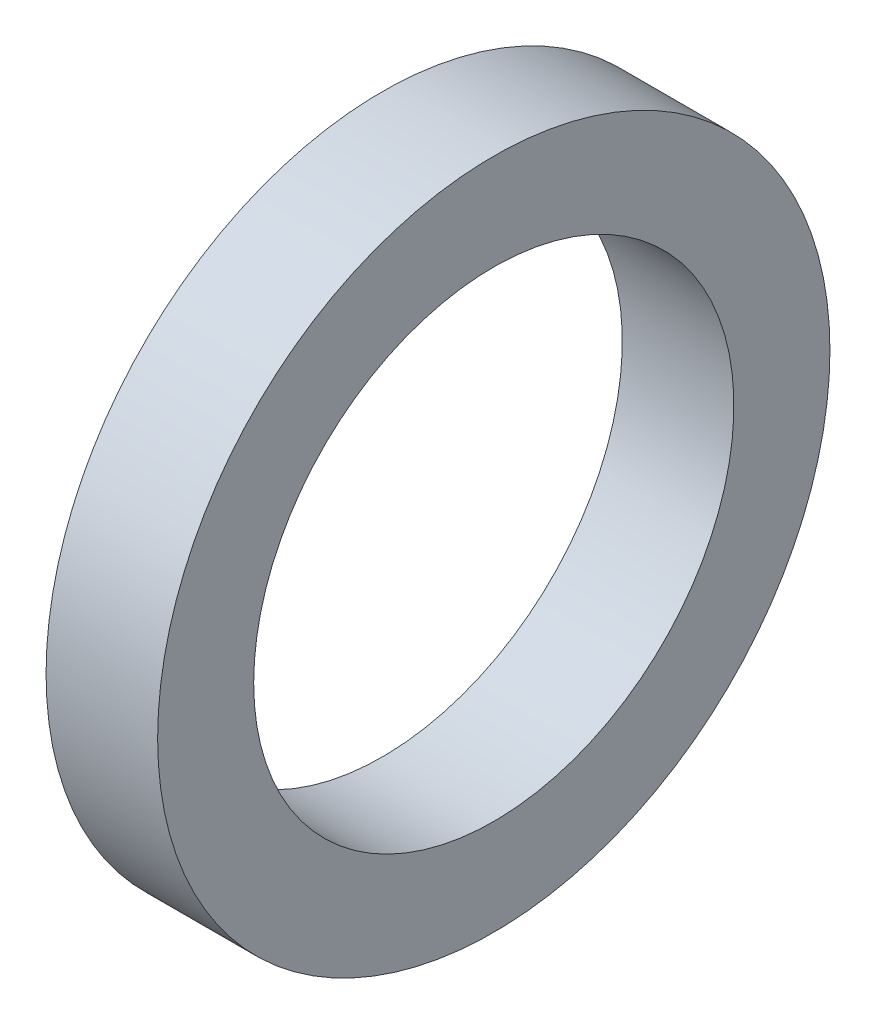
SolidWorks part; units mm, degrees
ref_plane "Front Plane" through (0, 0, 0) normal (0, 0, 1) x (1, 0, 0)
ref_plane "Top Plane" through (0, 0, 0) normal (0, 1, 0) x (1, 0, 0)
ref_plane "Right Plane" through (0, 0, 0) normal (1, 0, 0) x (0, 0, -1)
sketch "Sketch2" plane through (0, 0, 0) normal (0, 0, 1) x (1, 0, 0)
  line L0 (0, 0) -> (58.591, 0) construction
  line L2 (0, 0) -> (18.4, 0)
  line L3 (0, 0) -> (0, 2.5)
  line L4 (0, 2.5) -> (18.4, 2.5)
  line L5 (18.4, 0) -> (18.4, 2.5)
  line L6 (6, 2.5) -> (6, 6)
  line L11 (6, 6) -> (9.97, 6)
  line L16 (12.97, 6) -> (12.97, 3)
  line L17 (12.97, 3) -> (13.6304, 3)
  line L18 (13.6304, 3) -> (13.6304, 2.5)
  line L19 (13.6304, 2.5) -> (6, 2.5)
  line L22 (13.6304, 2.5) -> (16.1104, 2.5)
  line L23 (13.6304, 2.5) -> (13.6304, 4)
  line L24 (13.6304, 4) -> (16.1104, 4)
  line L25 (16.1104, 2.5) -> (16.1104, 4)
  line L27 (6, 6) -> (9.97, 6)
  line L28 (6, 6) -> (6, 9)
  line L29 (6, 9) -> (9.97, 9)
  line L30 (9.97, 6) -> (9.97, 9)
  line L31 (6, 9) -> (6, 8.25)
  line L32 (6, 8.25) -> (5, 8.25)
  line L33 (8.58, 22.001) -> (8.58, 12.476) construction
  line L34 (5, 12.476) -> (12.16, 12.476)
  line L35 (9.97, 9) -> (12.16, 9)
  line L36 (5, 7.5) -> (3, 7.5)
  line L37 (5, 8.25) -> (5, 12.476)
  line L38 (5, 7.5) -> (5, 14)
  line L39 (5, 14) -> (3, 14)
  line L40 (3, 7.5) -> (3, 14)
  line L41 (5, 22.001) -> (12.16, 22.001)
  line L42 (5, 22.001) -> (5, 30.1625)
  line L43 (5, 30.1625) -> (12.16, 30.1625)
  line L44 (12.16, 22.001) -> (12.16, 30.1625)
  line L49 (16.6304, 22.001) -> (16.6304, 7.5)
  line L51 (23.0104, 7.5) -> (23.0104, 6.5)
  line L54 (16.1104, 4) -> (13.6304, 4)
  line L56 (18.0304, 7.5) -> (23.0104, 7.5)
  line L57 (13.16, 22.001) -> (16.6304, 22.001)
  line L58 (16.1104, 3.5) -> (20.0104, 3.5)
  line L59 (29.9004, 14) -> (26.9004, 11)
  line L60 (4, 31.75) -> (18.0304, 31.75)
  line L61 (18.0304, 7.5) -> (23.0104, 7.5)
  line L62 (18.0304, 7.5) -> (18.0304, 12)
  line L63 (18.0304, 12) -> (23.0104, 12)
  line L64 (23.0104, 7.5) -> (23.0104, 12)
  line L65 (18.0304, 31.75) -> (18.0304, 12)
  line L66 (23.0104, 11) -> (26.9004, 11)
  line L67 (34.8004, 23) -> (31.3004, 19.5)
  line L68 (35.8004, 31) -> (38.7904, 33.99)
  line L69 (29.9004, 14) -> (29.9004, 15)
  line L70 (29.9004, 15) -> (22.9304, 15)
  line L71 (22.9304, 15) -> (21.0304, 15)
  line L72 (18.0304, 7.5) -> (16.6304, 7.5)
  line L73 (21.0304, 15) -> (21.0304, 43)
  line L74 (20.0304, 40) -> (10.0704, 40)
  line L75 (10.0704, 40) -> (4, 40)
  line L76 (21.0304, 43) -> (20.0304, 43)
  line L77 (22.9304, 15) -> (29.9004, 15)
  line L78 (22.9304, 15) -> (22.9304, 21)
  line L79 (22.9304, 21) -> (29.9004, 21)
  line L80 (29.9004, 15) -> (29.9004, 21)
  line L81 (10.0704, 40) -> (20.0304, 40)
  line L82 (10.0704, 40) -> (10.0704, 50)
  line L83 (10.0704, 50) -> (20.0304, 50)
  line L84 (20.0304, 40) -> (20.0304, 50)
  line L85 (4, 40) -> (4, 31.75)
  line L86 (12.97, 3) -> (12.97, 2.5)
  line L87 (31.3004, 19.5) -> (29.9004, 19.5)
  line L88 (21.51, 63.5) -> (21.51, 44)
  line L89 (21.51, 63.5) -> (25.9304, 63.5)
  line L90 (25.9304, 63.5) -> (25.9304, 25)
  line L91 (27.8304, 25) -> (25.9304, 25)
  line L92 (10.0704, 48) -> (9, 48)
  line L93 (9, 48) -> (9, 53.476)
  line L94 (9, 53.476) -> (20.0304, 53.476)
  line L95 (20.0304, 53.476) -> (20.0304, 50)
  line L96 (14.5152, 63.001) -> (14.5152, 53.476) construction
  line L97 (9, 63.001) -> (20.0304, 63.001)
  line L98 (9, 63.001) -> (9, 68.2625)
  line L99 (9, 68.2625) -> (20.0304, 68.2625)
  line L100 (20.0304, 63.001) -> (20.0304, 68.2625)
  line L101 (12.97, 6) -> (11.97, 6)
  line L102 (9, 42.5) -> (5, 42.5)
  line L103 (9, 42.5) -> (9, 55)
  line L104 (9, 55) -> (5, 55)
  line L105 (5, 42.5) -> (5, 55)
  line L106 (9.97, 6) -> (10.87, 6)
  line L107 (27.8304, 25) -> (34.8004, 25)
  line L108 (34.8004, 25) -> (34.8004, 23)
  line L109 (0, 0) -> (-2, 0)
  line L110 (0, 0) -> (0, 11)
  line L111 (27.8304, 25) -> (34.8004, 25)
  line L112 (27.8304, 25) -> (27.8304, 32.5)
  line L113 (27.8304, 32.5) -> (34.8004, 32.5)
  line L114 (34.8004, 25) -> (34.8004, 32.5)
  line L115 (35.8004, 31) -> (34.8004, 31)
  line L116 (27.8304, 32.5) -> (27.8304, 64.5)
  line L117 (21.1827, 74.025) -> (6.8477, 74.025)
  line L118 (6.8477, 74.025) -> (6.8477, 76.2)
  line L119 (38.7904, 47.29) -> (30.8304, 55.25)
  line L120 (0, 11) -> (-2, 11)
  line L121 (38.7904, 43.815) -> (30.8529, 43.815)
  line L123 (-4.8, 69.85) -> (1.55, 76.2)
  line L124 (38.7904, 47.29) -> (38.7904, 33.99)
  line L125 (-2, 0) -> (-2, 11)
  line L126 (38.7904, 37.465) -> (30.8529, 37.465)
  line L127 (30.8529, 43.815) -> (30.8529, 37.465)
  line L128 (6, 2.5) -> (6, 0)
  line L129 (0, 63.5) -> (0, 30)
  line L132 (5, 63.5) -> (0, 63.5)
  line L136 (-1.8, 30) -> (-11.76, 30)
  line L138 (-13.76, 25.4) -> (-2, 25.4)
  line L139 (-2, 25.4) -> (-2, 11.5)
  line L140 (27.8304, 64.5) -> (21.1827, 64.5)
  line L141 (-1.8, 30) -> (-11.76, 30)
  line L142 (-1.8, 30) -> (-1.8, 39)
  line L143 (-1.8, 39) -> (-11.76, 39)
  line L144 (-11.76, 30) -> (-11.76, 39)
  line L145 (21.1827, 64.5) -> (21.1827, 74.025)
  line L146 (-12.76, 37) -> (-12.76, 47.29)
  line L147 (-12.76, 37) -> (-11.76, 37)
  line L148 (30.8304, 55.25) -> (30.8304, 76.2)
  line L149 (11.97, 6) -> (11.97, 5.45)
  line L154 (-2, 11.5) -> (1, 11.5)
  line L155 (5, 60.6197) -> (24.05, 60.6197)
  line L160 (5, 60.6197) -> (5, 55.8572)
  line L161 (5, 55.8572) -> (24.05, 55.8572)
  line L166 (24.05, 60.6197) -> (24.05, 55.8572)
  line L167 (5, 60.6197) -> (24.05, 55.8572) construction
  line L172 (5, 55.8572) -> (24.05, 60.6197) construction
  line L173 (24.05, 62.2072) -> (25.9304, 62.2072)
  line L174 (11.97, 5.45) -> (10.87, 5.45)
  line L175 (10.87, 6) -> (10.87, 5.45)
  line L176 (24.05, 62.2072) -> (24.05, 54.2697)
  line L177 (24.05, 54.2697) -> (25.9304, 54.2697)
  line L178 (25.9304, 62.2072) -> (25.9304, 54.2697)
  line L179 (24.05, 62.2072) -> (25.9304, 54.2697) construction
  line L180 (24.05, 54.2697) -> (25.9304, 62.2072) construction
  line L181 (3, 19.6197) -> (15.7, 19.6197)
  line L182 (3, 19.6197) -> (3, 14.8572)
  line L183 (3, 14.8572) -> (15.7, 14.8572)
  line L184 (15.7, 19.6197) -> (15.7, 14.8572)
  line L185 (3, 19.6197) -> (15.7, 14.8572) construction
  line L186 (3, 14.8572) -> (15.7, 19.6197) construction
  line L187 (15.7, 21.2072) -> (16.6304, 21.2072)
  line L188 (15.7, 21.2072) -> (15.7, 13.2697)
  line L189 (15.7, 13.2697) -> (16.6304, 13.2697)
  line L190 (16.6304, 21.2072) -> (16.6304, 13.2697)
  line L191 (15.7, 21.2072) -> (16.6304, 13.2697) construction
  line L192 (15.7, 13.2697) -> (16.6304, 21.2072) construction
  line L193 (1, 11.5) -> (1, 6.5)
  line L194 (1, 6.5) -> (3, 6.5)
  line L195 (23.0104, 6.5) -> (20.0104, 3.5)
  line L196 (5, 63.5) -> (5, 42.5)
  line L197 (5, 42.5) -> (3, 42.5)
  line L198 (3, 42.5) -> (3, 6.5)
  line L199 (6, 0) -> (12.97, 0)
  line L200 (12.97, 0) -> (12.97, 2.5)
  line L201 (18.0304, 31.75) -> (18.0304, 35.875)
  line L202 (18.0304, 35.875) -> (21.0304, 35.875)
  line L203 (30.8304, 76.2) -> (6.8477, 76.2)
  line L204 (3.4027, 69.85) -> (7.8477, 69.85) construction
  line L205 (7.8477, 67.4687) -> (26.8977, 67.4688)
  line L206 (7.8477, 74.025) -> (7.8477, 64.5)
  line L207 (7.8477, 64.5) -> (-1.8, 64.5)
  line L208 (-1.8, 64.5) -> (-1.8, 39)
  line L209 (-12.76, 47.29) -> (-4.8, 55.25)
  line L210 (-4.8, 55.25) -> (-4.8, 69.85)
  line L211 (7.8477, 67.4687) -> (7.8477, 72.2313)
  line L212 (7.8477, 72.2313) -> (26.8977, 72.2313)
  line L213 (26.8977, 67.4688) -> (26.8977, 72.2313)
  line L214 (26.8977, 73.8187) -> (30.8304, 73.8187)
  line L215 (26.8977, 73.8187) -> (26.8977, 65.8813)
  line L216 (26.8977, 65.8813) -> (30.8304, 65.8813)
  line L217 (30.8304, 73.8187) -> (30.8304, 65.8813)
  line L218 (3.4027, 72.2313) -> (25.6277, 72.2313)
  line L219 (3.4027, 72.2313) -> (3.4027, 67.4687)
  line L220 (3.4027, 67.4687) -> (25.6277, 67.4687)
  line L221 (25.6277, 72.2313) -> (25.6277, 67.4687)
  line L222 (25.6277, 69.85) -> (21.1827, 69.85) construction
  line L223 (21.51, 44) -> (22.9304, 44)
  line L224 (22.9304, 44) -> (22.9304, 21)
  line L225 (13.6304, 4) -> (13.6304, 12.2697)
  line L226 (13.6304, 12.2697) -> (13.16, 12.2697)
  line L227 (13.16, 12.2697) -> (13.16, 22.001)
  line L228 (12.16, 9) -> (12.16, 12.476)
  line L229 (-1.8, 30) -> (0, 30)
  line L230 (9, 65.6317) -> (3.4027, 65.6317) construction
  line L231 (20.0304, 65.6317) -> (25.6277, 65.6317) construction
  line L232 (1.55, 76.2) -> (6.8477, 76.2)
  line L233 (-11.76, 30) -> (-13.76, 30)
  line L234 (-13.76, 30) -> (-13.76, 25.4)
  circle A0 centre (26.8804, 25.95) radius 0.95
  circle A1 centre (21.9804, 15.95) radius 0.95
  circle A2 centre (17.3304, 8.2) radius 0.7
  circle A3 centre (10.42, 6.45) radius 0.45
  circle A4 centre (-0.9, 30.9) radius 0.9
  point P7 (24.9902, 58.2385)
  point P131 (16.1652, 17.2385)
  point P135 (14.525, 58.2385)
  point P146 (9.35, 17.2385)
sketch "Sketch3" plane through (0, 0, 0) normal (0, 0, 1) x (1, 0, 0)
  line L0 (22.9304, 21) -> (29.9004, 21) construction
  line L1 (29.9004, 15) -> (29.9004, 21) construction
  line L2 (29.9004, 15) -> (22.9304, 15) construction
  line L3 (22.9304, 15) -> (22.9304, 21) construction
  line L4 (22.9304, 21) -> (29.9004, 21)
  line L5 (29.9004, 15) -> (29.9004, 21)
  line L6 (29.9004, 15) -> (22.9304, 15)
  line L7 (22.9304, 15) -> (22.9304, 21)
revolve "Revolve1" add sketch "Sketch3" angle 360 about L0
